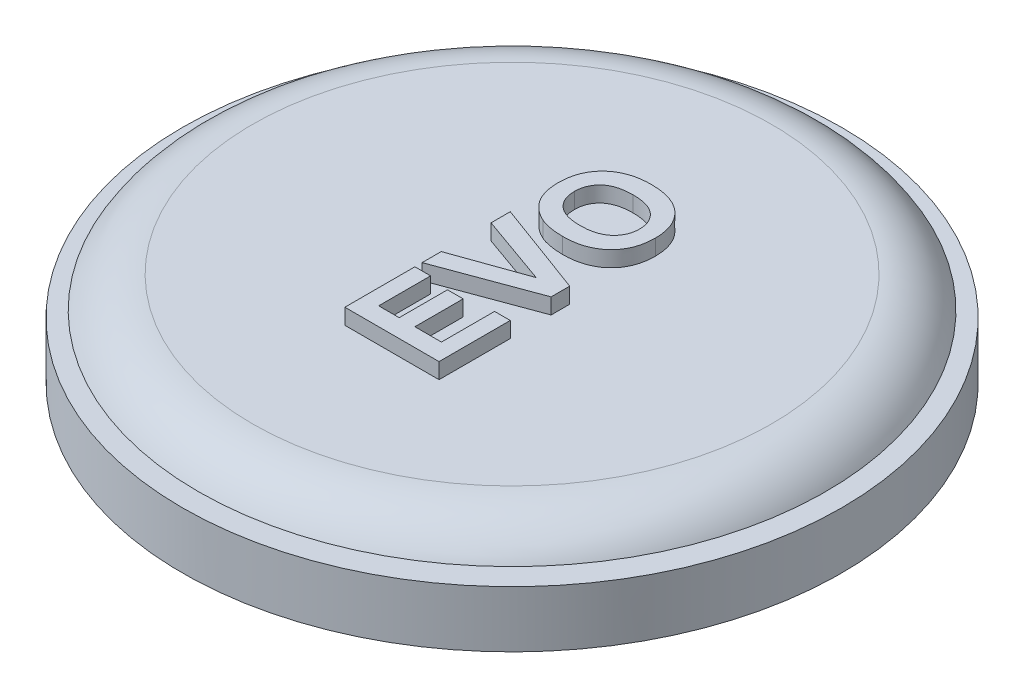
SolidWorks part; units mm, degrees
ref_plane "Спереди" through (0, 0, 0) normal (0, 0, 1) x (1, 0, 0)
ref_plane "Сверху" through (0, 0, 0) normal (0, 1, 0) x (1, 0, 0)
ref_plane "Справа" through (0, 0, 0) normal (1, 0, 0) x (0, 0, -1)
sketch "Sketch1" plane through (0, 0, 0) normal (0, 1, 0) x (1, 0, 0)
  circle A0 centre (0, 0) radius 17.3
  dimension "D1" = 34.6
extrude "Boss-Extrude1" add sketch "Sketch1" along normal blind 4
sketch "Sketch2" plane through (0, 4, 0) normal (0, 1, 0) x (1, 0, 0)
  circle A0 centre (0, 0) radius 20
  dimension "D1" = 40
extrude "Boss-Extrude2" add sketch "Sketch2" along normal blind 2
chamfer "Chamfer1" distance 0.5 angle 70 1 edges at (0, 0, 17.3) first distance on face at (0, 0, 17.3)
sketch "Sketch3" plane through (0, 6, 0) normal (0, 1, 0) x (1, 0, 0)
  line L0 (3.5, -19.6914) -> (3.5, 19.6914) construction
  line L1 (0, -20) -> (0, 20) construction
  circle A0 centre (0, 0) radius 20 construction
  text T0 "EVO" font "Arial" height 6
  dimension "D1" = 3.5
extrude "Boss-Extrude3" add sketch "Sketch3" along normal blind 1
sketch "Sketch4" plane through (0, 0, 0) normal (0, -1, 0) x (1, 0, 0)
  circle A0 centre (0, 0) radius 17.8
  circle A1 centre (0, 0) radius 21
  circle A2 centre (0, 0) radius 16.8 construction
  circle A3 centre (0, 0) radius 20 construction
  dimension "D1" = 1
  dimension "D2" = 1
extrude "Boss-Extrude4" add sketch "Sketch4" against normal offset from surface (3.6 mm away) 0.4 separate body up to face at (0, 4, 17.3)
fillet "Fillet1" radius 4 1 edges at (0, 6, 20)
